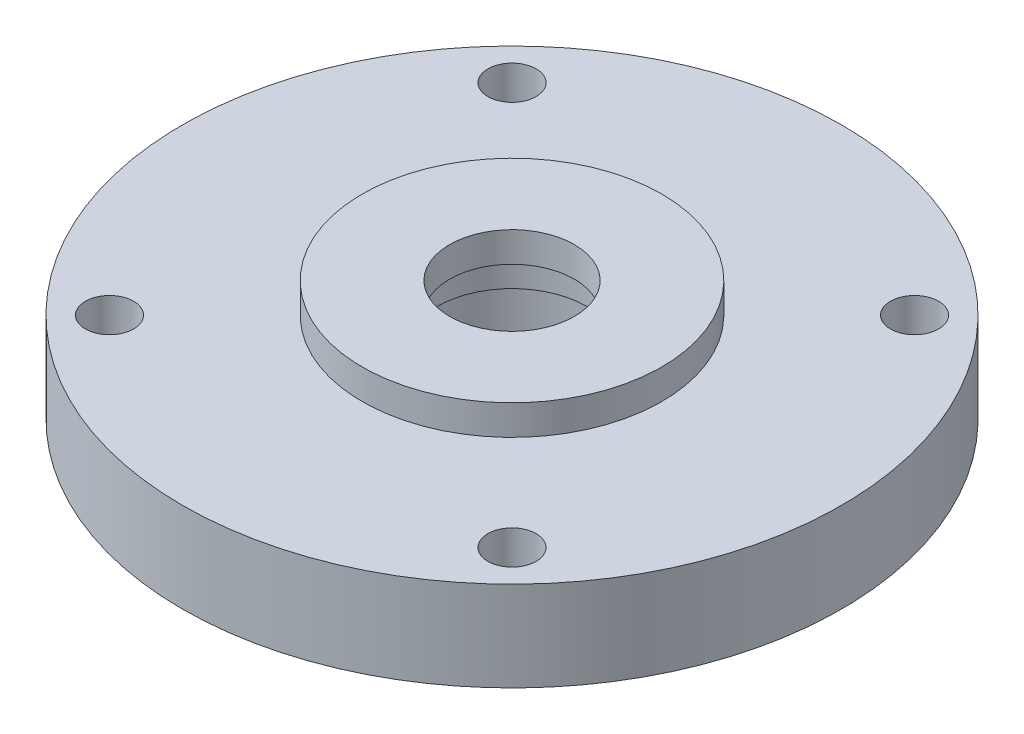
SolidWorks part; units mm, degrees
other "Markup1"
sketch "Sketch2" plane through (28.575, 0, 28.575) normal (0.2444, -0.6972, 0.6739) x (0.9588, 0.0701, -0.2753)
material "6061-T6 (SS)"
ref_plane "Front Plane" through (0, 0, 0) normal (0, 0, 1) x (1, 0, 0)
ref_plane "Top Plane" through (0, 0, 0) normal (0, 1, 0) x (1, 0, 0)
ref_plane "Right Plane" through (0, 0, 0) normal (1, 0, 0) x (0, 0, -1)
sketch "Sketch1" plane through (0, 0, 0) normal (0, 0, 1) x (1, 0, 0)
  line L0 (0, 0) -> (0, 12.7) construction
  line L3 (-15.875, 12.7) -> (-6.604, 12.7)
  line L4 (-6.604, 12.7) -> (-6.604, 9.525)
  line L5 (-6.604, 9.525) -> (-7.9375, 9.525)
  line L6 (-7.9375, 9.525) -> (-7.9375, 6.35)
  line L7 (-15.875, 12.7) -> (-15.875, 9.525)
  line L8 (-15.875, 9.525) -> (-34.925, 9.525)
  line L9 (-34.925, 9.525) -> (-34.925, 0)
  line L10 (-7.9375, 6.35) -> (-9.515, 6.35)
  line L15 (-20.6375, 0) -> (-9.515, 0)
  line L16 (-9.515, 0) -> (-9.515, 6.35)
  line L17 (-34.925, 0) -> (-25.4, 0)
  line L18 (-25.4, 0) -> (-25.4, 3.1369)
  line L19 (-25.4, 3.1369) -> (-20.6375, 3.1369)
  line L20 (-20.6375, 3.1369) -> (-20.6375, 0)
  dimension "D1" = 13.208
  dimension "D2" = 19.03
  dimension "D3" = 15.875
  dimension "D4" = 3.175
  dimension "D5" = 3.175
  dimension "D6" = 19.05
  dimension "D7" = 69.85
  dimension "D8" = 3.175
  dimension "D9" = 4.7625
  dimension "D10" = 6.35
  dimension "D12" = 50.8
  dimension "D13" = 3.1369
revolve "Revolve1" add sketch "Sketch1" angle 360 about L0
hole_wizard "#10 Clearance Hole1" positions "Sketch3" profile "Sketch4" hole size "#10" standard "ANSI Inch"
sketch "Sketch3" plane through (0, 9.525, 0) normal (0, 1, 0) x (1, 0, 0)
  line L0 (-21.3281, 21.3281) -> (21.3281, -21.3281) construction
  line L1 (-21.3281, -21.3281) -> (21.3281, 21.3281) construction
  line L2 (0, 0) -> (-34.925, 0) construction
  circle A0 centre (0, 0) radius 34.925 construction
  point P0 (-21.3281, 21.3281)
  point P2 (21.3281, 21.3281)
  point P4 (21.3281, -21.3281)
  point P6 (-21.3281, -21.3281)
  point P14 (0, 0)
  point P16 (0, 0)
  dimension "D1" = 45
  dimension "D2" = 60.325
sketch "Sketch4" plane through (-21.3281, 9.525, -21.3281) normal (1, 0, 0) x (0, 0, 1)
  line L0 (0, 0) -> (0, 12.7574)
  line L1 (0, 12.7574) -> (2.5527, 11.2236)
  line L2 (2.5527, 11.2236) -> (2.5527, 0)
  line L5 (2.5527, 0) -> (0, 0)
  line L10 (0, 12.7574) -> (-2.5527, 11.2236) construction
  line L11 (0, -6.35) -> (0, 107.95) construction
  dimension "Hole Dia." = 5.1054
  dimension "Hole Depth" = 12.7574
  dimension "Drill Angle" = 118
sketch "Sketch5" plane through (0, 0, 0) normal (0, 1, 0) x (1, 0, 0)
  circle A0 centre (0, 0) radius 38.1
  dimension "D1" = 76.2
ref_plane "Plane1" through (0, 0, 0) normal (0, -1, 0) x (-1, 0, 0)
